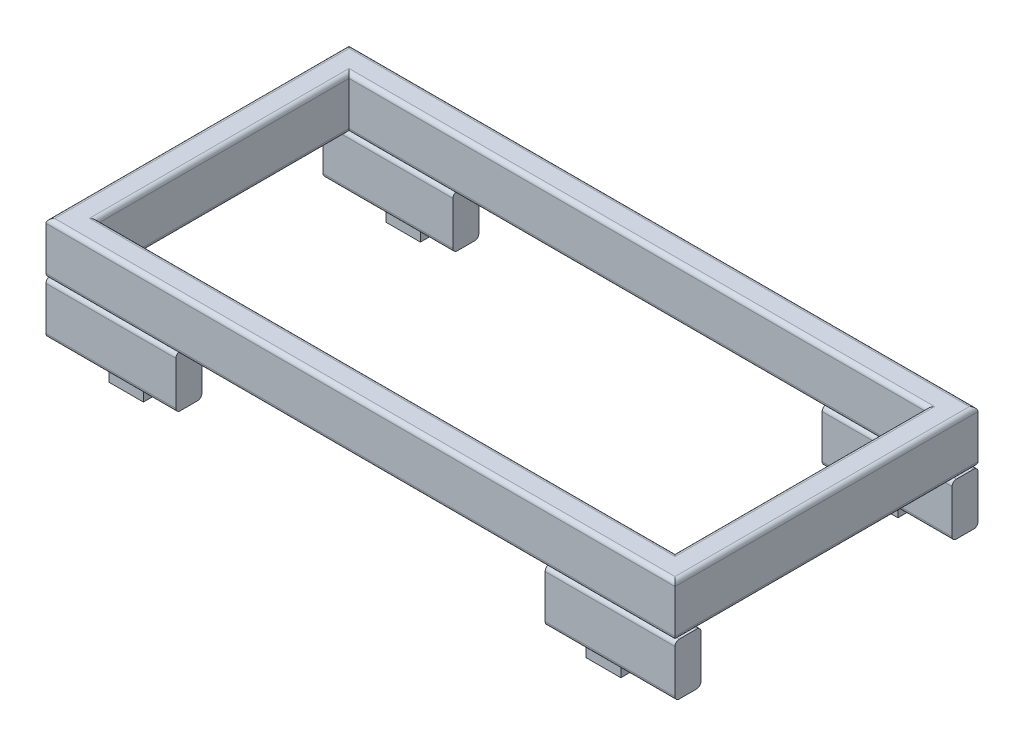
SolidWorks part; units mm, degrees
material "V2a"
ref_plane "Vorne" through (0, 0, 0) normal (0, 0, 1) x (1, 0, 0)
ref_plane "Oben" through (0, 0, 0) normal (0, 1, 0) x (1, 0, 0)
ref_plane "Rechts" through (0, 0, 0) normal (1, 0, 0) x (0, 0, -1)
sketch "Skizze1" plane through (0, 0, 0) normal (0, 1, 0) x (1, 0, 0)
  line L0 (0, 350) -> (0, -350) construction
  line L1 (-726.5, 350) -> (726.5, 350)
  line L2 (-726.5, 350) -> (-726.5, -350)
  line L3 (-726.5, -350) -> (726.5, -350)
  line L4 (726.5, 350) -> (726.5, -350)
  line L5 (-666.5, 290) -> (666.5, 290)
  line L6 (666.5, 290) -> (666.5, -290)
  line L7 (-666.5, -290) -> (666.5, -290)
  line L8 (-666.5, 290) -> (-666.5, -290)
  dimension "D1" = 700
  dimension "D2" = 1453
  dimension "D3" = 60
extrude "Aufsatz-Linear austragen1" add sketch "Skizze1" along normal mid plane 120
fillet "Verrundung1" radius 10 16 edges at (0, -60, -290) (666.5, -60, 0) (0, -60, 290) (-666.5, -60, 0) (0, -60, 350) (726.5, -60, 0) (0, -60, -350) (-726.5, -60, 0) (666.5, 60, 0) (0, 60, -290) (-666.5, 60, 0) (0, 60, 290) (0, 60, -350) (726.5, 60, 0) (0, 60, 350) (-726.5, 60, 0)
sketch "Skizze2" plane through (0, -60, 0) normal (0, -1, 0) x (1, 0, 0)
  line L0 (666.5, 290) -> (-666.5, 290) construction
  line L1 (-726.5, 350) -> (-426.5, 350)
  line L2 (-726.5, 350) -> (-726.5, 290)
  line L3 (-726.5, 290) -> (-426.5, 290)
  line L4 (-426.5, 350) -> (-426.5, 290)
  line L5 (726.5, 350) -> (426.5, 350)
  line L6 (726.5, 350) -> (726.5, 290)
  line L7 (726.5, 290) -> (426.5, 290)
  line L8 (426.5, 350) -> (426.5, 290)
  line L9 (726.5, -350) -> (426.5, -350)
  line L10 (726.5, -350) -> (726.5, -290)
  line L11 (726.5, -290) -> (426.5, -290)
  line L12 (426.5, -350) -> (426.5, -290)
  line L13 (-726.5, -350) -> (-426.5, -350)
  line L14 (-726.5, -350) -> (-726.5, -290)
  line L15 (-726.5, -290) -> (-426.5, -290)
  line L16 (-426.5, -350) -> (-426.5, -290)
  line L17 (-666.5, -290) -> (666.5, -290) construction
  dimension "D1" = 300
extrude "Aufsatz-Linear austragen2" add sketch "Skizze2" along normal blind 120
fillet "Verrundung3" radius 10 8 edges at (576.5, -180, 290) (576.5, -180, 350) (576.5, -180, -350) (576.5, -180, -290) (-576.5, -180, -350) (-576.5, -180, -290) (-576.5, -180, 290) (-576.5, -180, 350)
fillet "Verrundung4" radius 10 8 edges at (-721.5, -60, -290) (-576.5, -60, -350) (576.5, -60, -350) (551.5, -60, -290) (576.5, -60, 350) (551.5, -60, 290) (-551.5, -60, 290) (-576.5, -60, 350)
sketch "Skizze3" plane through (0, -180, 0) normal (0, -1, 0) x (1, 0, 0)
  line L0 (-726.5, 320) -> (726.5, 320) construction
  line L1 (-726.5, 340) -> (-726.5, 300) construction
  line L2 (726.5, 300) -> (726.5, 340) construction
  line L3 (726.5, -320) -> (-726.5, -320) construction
  line L4 (726.5, -340) -> (726.5, -300) construction
  line L5 (-726.5, -300) -> (-726.5, -340) construction
  circle A0 centre (-619.5, 320) radius 8.75
  circle A1 centre (-619.5, -320) radius 8.75
  circle A2 centre (619.5, 320) radius 8.75
  circle A3 centre (619.5, -320) radius 8.75
  dimension "D3" = 17.5
  dimension "D1" = 107
  dimension "D2" = 107
extrude "Schnitt-Linear austragen1" cut sketch "Skizze3" against normal blind 120
sketch "Skizze4" plane through (0, -180, 0) normal (0, -1, 0) x (1, 0, 0)
  line L1 (-591.5, 340) -> (-511.5, 340)
  line L2 (-591.5, 340) -> (-591.5, 300)
  line L3 (-591.5, 300) -> (-511.5, 300)
  line L4 (-511.5, 340) -> (-511.5, 300)
  line L5 (511.5, 340) -> (591.5, 340)
  line L6 (511.5, 340) -> (511.5, 300)
  line L7 (511.5, 300) -> (591.5, 300)
  line L8 (591.5, 340) -> (591.5, 300)
  line L9 (511.5, -300) -> (591.5, -300)
  line L10 (511.5, -300) -> (511.5, -340)
  line L11 (511.5, -340) -> (591.5, -340)
  line L12 (591.5, -300) -> (591.5, -340)
  line L13 (-591.5, -300) -> (-511.5, -300)
  line L14 (-591.5, -300) -> (-591.5, -340)
  line L15 (-591.5, -340) -> (-511.5, -340)
  line L16 (-511.5, -300) -> (-511.5, -340)
  line L17 (-726.5, -320) -> (726.5, -320) construction
  line L18 (-726.5, -300) -> (-726.5, -340) construction
  line L19 (726.5, -340) -> (726.5, -300) construction
  line L20 (-726.5, 320) -> (726.5, 320) construction
  line L21 (-726.5, 340) -> (-726.5, 300) construction
  line L22 (726.5, 300) -> (726.5, 340) construction
  dimension "D1" = 80
  dimension "D2" = 40
  dimension "D3" = 135
  dimension "D4" = 135
extrude "Aufsatz-Linear austragen3" add sketch "Skizze4" along normal blind 25
